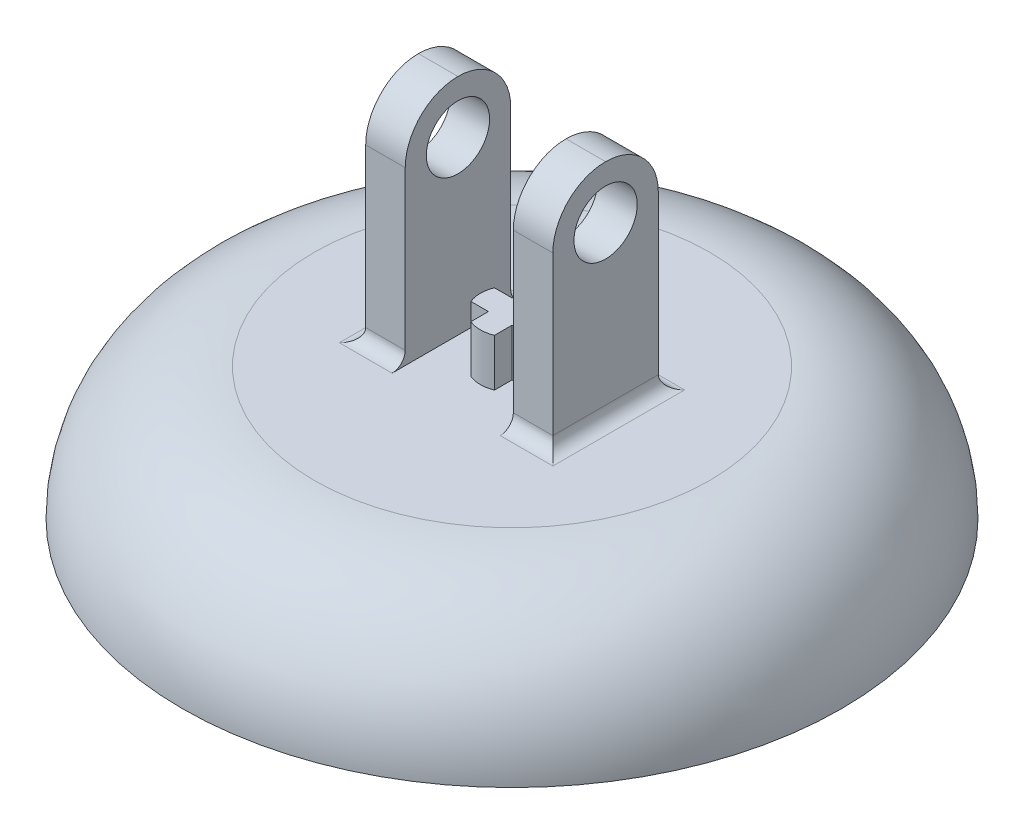
SolidWorks part; units mm, degrees
ref_plane "Front Plane" through (0, 0, 0) normal (0, 0, 1) x (1, 0, 0)
ref_plane "Top Plane" through (0, 0, 0) normal (0, 1, 0) x (1, 0, 0)
ref_plane "Right Plane" through (0, 0, 0) normal (1, 0, 0) x (0, 0, -1)
sketch "Sketch1" plane through (0, 0, 0) normal (0, 1, 0) x (1, 0, 0)
  circle A0 centre (0, 0) radius 25
  dimension "D1" = 50
extrude "Boss-Extrude1" add sketch "Sketch1" along normal blind 10
fillet "Fillet1" radius 10 1 edges at (0, 10, 25)
sketch "Sketch2" plane through (0, 10, 0) normal (0, 1, 0) x (1, 0, 0)
  line L7 (-2.2269, -0.895) -> (-0.895, -0.895)
  line L8 (-0.895, -2.2269) -> (-0.895, -0.895)
  line L11 (-2.2269, 0.895) -> (-0.895, 0.895)
  line L12 (-0.895, 2.2269) -> (-0.895, 0.895)
  line L15 (2.2269, 0.895) -> (0.895, 0.895)
  line L16 (0.895, 2.2269) -> (0.895, 0.895)
  line L19 (2.2269, -0.895) -> (0.895, -0.895)
  line L20 (0.895, -2.2269) -> (0.895, -0.895)
  arc A0 (2.2269, -0.895) -> (2.2269, 0.895) centre (0, 0) ccw
  arc A1 (-0.895, -2.2269) -> (0.895, -2.2269) centre (0, 0) ccw
  arc A2 (-2.2269, 0.895) -> (-2.2269, -0.895) centre (0, 0) ccw
  arc A3 (0.895, 2.2269) -> (-0.895, 2.2269) centre (0, 0) ccw
  dimension "D1" = 4.8
  dimension "D2" = 0.895
  dimension "D3" = 0.895
  dimension "D4" = 0.895
  dimension "D5" = 0.895
  dimension "D6" = 1.79
  dimension "D7" = 1.79
  dimension "D8" = 1.79
  dimension "D9" = 1.79
extrude "Boss-Extrude2" add sketch "Sketch2" along normal blind 3.6
sketch "Sketch3" plane through (0, 0, 0) normal (0, -1, 0) x (1, 0, 0)
  line L1 (-7.1, 4) -> (-4.1, 4)
  line L2 (-7.1, 4) -> (-7.1, -4)
  line L3 (-7.1, -4) -> (-4.1, -4)
  line L4 (-4.1, 4) -> (-4.1, -4)
  line L5 (4.1, 4) -> (7.1, 4)
  line L6 (4.1, 4) -> (4.1, -4)
  line L7 (4.1, -4) -> (7.1, -4)
  line L8 (7.1, 4) -> (7.1, -4)
  dimension "D1" = 3
  dimension "D2" = 3
  dimension "D3" = 4.1
  dimension "D4" = 4.1
  dimension "D5" = 4
  dimension "D6" = 4
  dimension "D7" = 4
  dimension "D8" = 4
extrude "Boss-Extrude3" add sketch "Sketch3" against normal blind 27
sketch "Sketch4" plane through (7.1, 0, 0) normal (1, 0, 0) x (0, 0, -1)
  line L0 (-4, 27) -> (-4, 10) construction
  line L1 (-25, 0) -> (25, 0) construction
  circle A0 centre (0, 23) radius 2.4
  dimension "D1" = 4.8
  dimension "D2" = 4
  dimension "D3" = 23
extrude "Cut-Extrude1" cut sketch "Sketch4" against normal through all
fillet "Fillet2" radius 4 4 edges at (5.6, 27, -4) (5.6, 27, 4) (-5.6, 27, 4) (-5.6, 27, -4)
fillet "Fillet3" radius 1 6 edges at (-5.6, 10, -4) (-7.1, 10, 0) (-5.6, 10, 4) (5.6, 10, 4) (7.1, 10, 0) (5.6, 10, -4)
